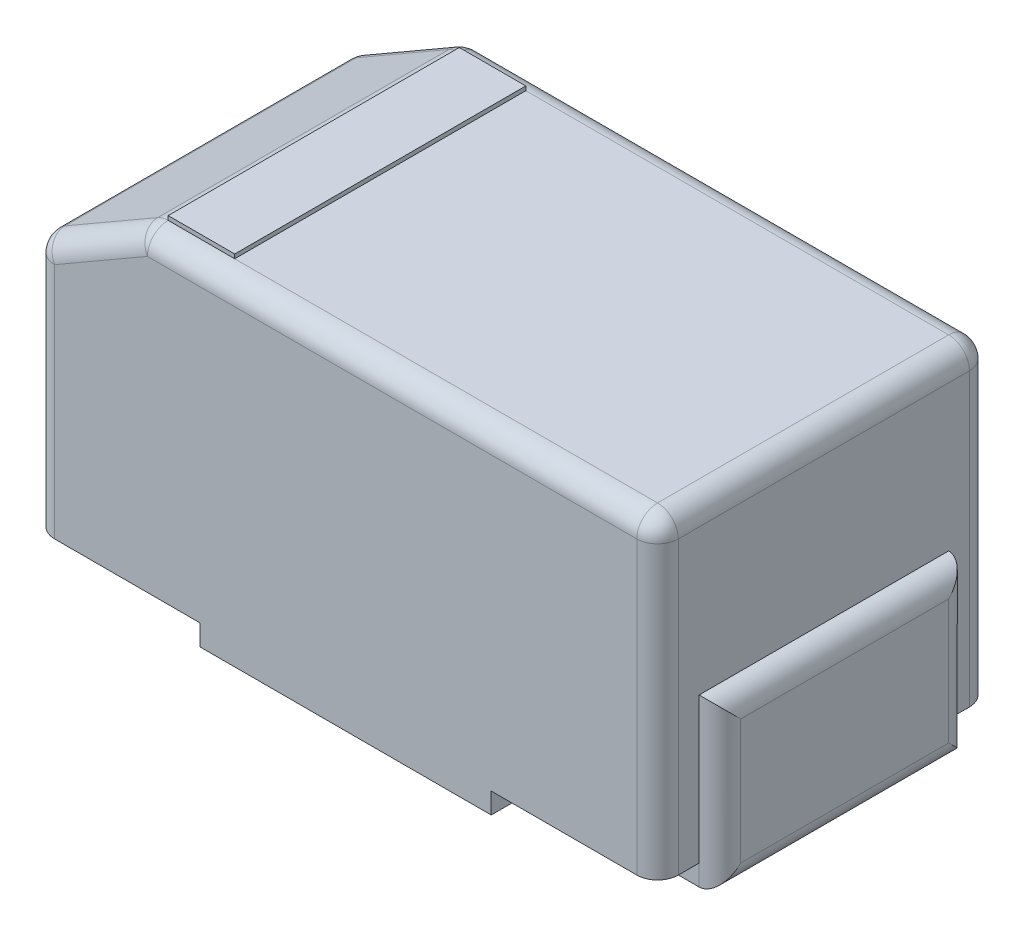
SolidWorks part; units mm, degrees
ref_plane "Спереди" through (0, 0, 0) normal (0, 0, 1) x (1, 0, 0)
ref_plane "Сверху" through (0, 0, 0) normal (0, 1, 0) x (1, 0, 0)
ref_plane "Справа" through (0, 0, 0) normal (1, 0, 0) x (0, 0, -1)
sketch "Эскиз1" plane through (0, 0, 0) normal (0, 1, 0) x (1, 0, 0)
  line L1 (-1.5, -0.8) -> (1.5, -0.8)
  line L2 (-1.5, -0.8) -> (-1.5, 0.8)
  line L3 (-1.5, 0.8) -> (1.5, 0.8)
  line L4 (1.5, -0.8) -> (1.5, 0.8)
  line L5 (-1.5, -0.8) -> (1.5, 0.8) construction
  line L6 (-1.5, 0.8) -> (1.5, -0.8) construction
  point P0 (0, 0)
  dimension "Длинна керамики" = 3
  dimension "Ширина керамики" = 1.6
sketch "Эскиз2" plane through (0, 0, 0) normal (0, 0, 1) x (1, 0, 0)
  line L0 (0, 0) -> (0, 1.6) construction
  line L1 (-1.5, 0) -> (1.5, 0) construction
  point P4 (0, 0)
  dimension "Высота керамики" = 1.6
extrude "Бобышка-Вытянуть1" add sketch "Эскиз1" along normal up to vertex (1.6 mm away) up to point (0, 1.6, 0)
sketch "Эскиз3" plane through (0, 0, 0) normal (0, -1, 0) x (1, 0, 0)
  line L0 (1.5, -0.8) -> (-1.5, -0.8) construction
  line L1 (-1.5, 0.8) -> (-0.7, 0.8)
  line L2 (-1.5, 0.8) -> (-1.5, -0.8)
  line L3 (-1.5, -0.8) -> (-0.7, -0.8)
  line L4 (-0.7, 0.8) -> (-0.7, -0.8)
  dimension "Ширина выреза" = 0.8
sketch "Эскиз4" plane through (0, 0, 0) normal (0, 0, 1) x (1, 0, 0)
  line L0 (0, 0) -> (0, 0.1) construction
  point P3 (0, 0)
  point P4 (0, 0)
  point P5 (0, 0)
  point P6 (0, 0)
  dimension "Высота выреза" = 0.1
extrude "Бобышка-Вытянуть2" add sketch "Эскиз3" against normal up to vertex (0.1 mm away) separate body up to point (0, 0.1, 0)
mirror "Зеркальное отражение1" about plane through (0, 0, 0) normal (1, 0, 0) of bodies 106
combine bodies "Соединить1" operation type subtract main body 104 bodies to subtract 106 107
sketch "Эскиз5" plane through (0, 0, 0) normal (0, 0, 1) x (1, 0, 0)
  line L0 (-0.7, 0.1) -> (-1.5, 0.1)
  line L1 (-1.5, 0.1) -> (-1.5, 0.8)
  line L2 (-1.5, 1.6) -> (-1.5, 0.1) construction
  line L3 (-1.5, 0.8) -> (-1.6, 0.8)
  line L4 (-1.6, 0.8) -> (-1.6, 0)
  line L5 (-1.6, 0) -> (-0.7, 0)
  line L6 (0, 0) -> (0, 0.8921) construction
  line L8 (-0.7, 0.1) -> (-0.7, 0)
  line L9 (1.5, 0.1) -> (1.5, 0.8)
  line L10 (0.7, 0.1) -> (1.5, 0.1)
  line L11 (0.7, 0.1) -> (0.7, 0)
  line L12 (1.6, 0) -> (0.7, 0)
  line L13 (1.6, 0.8) -> (1.6, 0)
  line L14 (1.5, 0.8) -> (1.6, 0.8)
  dimension "Толщина контакта" = 0.1
  dimension "Высота контакта" = 0.8
sketch "Эскиз6" plane through (0, 0, 0) normal (0, 1, 0) x (1, 0, 0)
  line L0 (0, -0.6) -> (0, 0.6) construction
  point P3 (0, 0)
  point P4 (0, 0)
  point P5 (0, 0)
  dimension "Ширина площадки" = 1.2
extrude "Бобышка-Вытянуть3" add sketch "Эскиз5" along normal up to vertex (0.6 mm away) and the other way up to vertex (0.6 mm away) separate body up to point (0, 0, 0.6) other way up to point (0, 0, -0.6)
chamfer "Фаска1" distance 0.3 angle 60 1 edges at (-1.5, 1.6, 0) first distance on face at (-1.5, 0.85, 0)
fillet "Скругление1" radius 0.1 11 edges at (-1.5, 1.3, 0) (-1.5, 0.7, -0.8) (-1.2402, 1.45, -0.8) (1.5, 0.85, -0.8) (-1.5, 0.7, 0.8) (-1.2402, 1.45, 0.8) (1.5, 0.85, 0.8) (1.5, 1.6, 0) (-0.9804, 1.6, 0) (0.2598, 1.6, 0.8) (0.2598, 1.6, -0.8)
sketch "Эскиз7" plane through (0, 1.6, 0) normal (0, 1, 0) x (1, 0, 0)
  line L2 (1.4, 0.7) -> (-0.9536, 0.7) construction
  line L3 (-0.9536, 0.7) -> (-0.6336, 0.7)
  line L4 (-0.9536, 0.7) -> (-0.9536, -0.7)
  line L5 (-0.9536, -0.7) -> (-0.6336, -0.7)
  line L6 (-0.6336, 0.7) -> (-0.6336, -0.7)
  line L7 (-0.9536, -0.7) -> (1.4, -0.7) construction
  point P0 (0, 0)
  point P13 (0, 0)
  dimension "Ширина ключа" = 0.32
extrude "Бобышка-Вытянуть4" add sketch "Эскиз7" along normal blind 0.02 separate body
fillet "Скругление2" radius 0.1 4 edges at (1.6, 0.4, -0.6) (1.6, 0, 0) (1.6, 0.4, 0.6) (1.6, 0.8, 0)
fillet "Скругление3" radius 0.1 4 edges at (-1.6, 0, 0) (-1.6, 0.4, 0.6) (-1.6, 0.8, 0) (-1.6, 0.4, -0.6)
